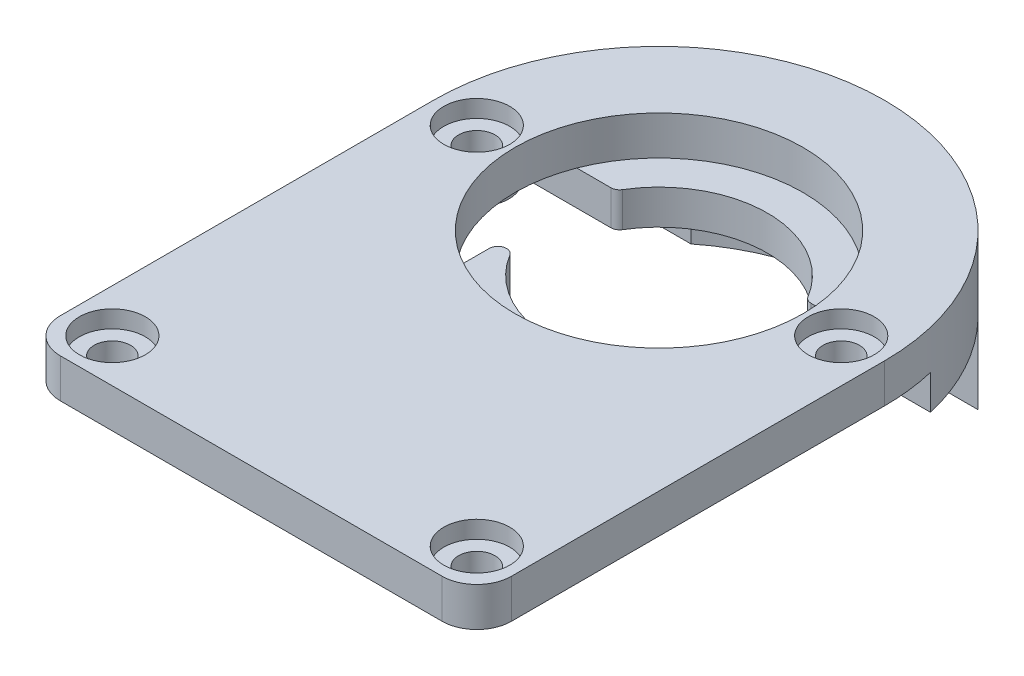
SolidWorks part; units mm, degrees
material "ABS"
ref_plane "正面" through (0, 0, 0) normal (0, 0, 1) x (1, 0, 0)
ref_plane "平面" through (0, 0, 0) normal (0, 1, 0) x (1, 0, 0)
ref_plane "右側面" through (0, 0, 0) normal (1, 0, 0) x (0, 0, -1)
sketch "ｽｹｯﾁ1" plane through (0, 0, 0) normal (0, 1, 0) x (1, 0, 0)
  line L1 (-13, 10.5) -> (13, 10.5)
  line L2 (-13, 10.5) -> (-13, -13)
  line L3 (-13, -13) -> (13, -13)
  line L4 (13, 10.5) -> (13, -13)
  line L5 (-13, 10.5) -> (13, -13) construction
  line L6 (-13, -13) -> (13, 10.5) construction
  circle A0 centre (0, 10.5) radius 13
  circle A1 centre (0, 10.5) radius 8.3
  point P0 (0, -1.25)
  dimension "D1" = 26
  dimension "D3" = 16.6
  dimension "D2" = 23.5
  dimension "D4" = 0
  dimension "D5" = 13
extrude "ﾎﾞｽ - 押し出し1" add sketch "ｽｹｯﾁ1" along normal blind 2.25 contours L1 A0 | L1 A0 | A0 L2 L3 L4 region at (0, 0, -19.0907) region at (10.65, 0, -10.2093) region at (0, 0, 6.0383)
sketch "ｽｹｯﾁ2" plane through (0, 0, 0) normal (0, -1, 0) x (1, 0, 0)
  line L0 (-12.6491, -13.5) -> (-5.4829, -13.5)
  line L1 (-13, 13) -> (13, 13) construction
  line L2 (5.4829, -13.5) -> (12.6491, -13.5)
  arc A0 (-12.6491, -13.5) -> (12.6491, -13.5) centre (0, -10.5) ccw
  arc A1 (-5.4829, -13.5) -> (5.4829, -13.5) centre (0, -10.5) ccw
  circle A2 centre (0, -10.5) radius 8.3 construction
  dimension "D1" = 26
  dimension "D3" = 12.5
  dimension "D2" = 26.5
extrude "ﾎﾞｽ - 押し出し2" add sketch "ｽｹｯﾁ2" along normal blind 2
sketch "ｽｹｯﾁ3" plane through (0, -2, 0) normal (0, -1, 0) x (1, 0, 0)
  line L0 (-9.3808, -19.5) -> (-7.1589, -19.5)
  line L1 (7.1589, -19.5) -> (9.3808, -19.5)
  arc A0 (-9.3808, -19.5) -> (9.3808, -19.5) centre (0, -10.5) ccw
  arc A1 (-7.1589, -19.5) -> (7.1589, -19.5) centre (0, -10.5) ccw
  dimension "D1" = 26
  dimension "D2" = 23
  dimension "D3" = 9
extrude "ﾎﾞｽ - 押し出し3" add sketch "ｽｹｯﾁ3" along normal blind 4.5
sketch "ｽｹｯﾁ4" plane through (0, 0, 0) normal (0, -1, 0) x (1, 0, 0)
  line L1 (-6.25, 6.25) -> (6.25, 6.25)
  line L5 (-6.25, 6.25) -> (6.25, -6.25) construction
  line L6 (-6.25, -6.25) -> (6.25, 6.25) construction
  line L8 (-6.25, -10.5) -> (-6.25, 6.25)
  line L9 (6.25, 6.25) -> (6.25, -10.5)
  arc A0 (6.25, -10.5) -> (-6.25, -10.5) centre (0, -10.5) ccw
  point P0 (0, 0)
  dimension "D2" = 12.5
  dimension "D1" = 12.5
  dimension "D3" = 6.25
extrude "ﾎﾞｽ - 押し出し4" add sketch "ｽｹｯﾁ4" along normal up to surface (2 mm away) up to face at (0, -2, -17.2734)
fillet "ﾌｨﾚｯﾄ1" radius 0.5 4 edges at (-6.25, -1, -10.5) (6.25, -1, -10.5) (-5.4829, -1, -13.5) (5.4829, -1, -13.5)
sketch "ｽｹｯﾁ5" plane through (0, 0, 0) normal (0, -1, 0) x (1, 0, 0)
  line L1 (-10.5, 10.5) -> (10.5, 10.5) construction
  line L2 (-10.5, 10.5) -> (-10.5, -10.5) construction
  line L3 (-10.5, -10.5) -> (10.5, -10.5) construction
  line L4 (10.5, 10.5) -> (10.5, -10.5) construction
  line L5 (-10.5, 10.5) -> (10.5, -10.5) construction
  line L6 (-10.5, -10.5) -> (10.5, 10.5) construction
  circle A0 centre (-10.5, 10.5) radius 1.85
  circle A1 centre (10.5, 10.5) radius 1.85
  circle A2 centre (-10.5, -10.5) radius 1.85
  circle A3 centre (10.5, -10.5) radius 1.85
  point P0 (0, 0)
  dimension "D2" = 3.7
  dimension "D3" = 3.7
  dimension "D4" = 3.7
  dimension "D5" = 3.7
  dimension "D1" = 21
extrude "ﾎﾞｽ - 押し出し5" add sketch "ｽｹｯﾁ5" along normal blind 0.5
hole_wizard "M2 丸平ねじ用座ぐり穴1" positions "ｽｹｯﾁ6" profile "ｽｹｯﾁ7" counterbore size "M2" standard "JIS" end condition up to next
sketch "ｽｹｯﾁ6" plane through (0, 2.25, 0) normal (0, 1, 0) x (1, 0, 0)
  point P0 (10.5, 10.5)
  point P3 (-10.5, 10.5)
  point P6 (-10.5, -10.5)
  point P9 (10.5, -10.5)
sketch "ｽｹｯﾁ7" plane through (10.5, 2.25, -10.5) normal (1, 0, 0) x (0, 0, 1)
  line L0 (0, 0) -> (0, 2.75)
  line L1 (0, 2.75) -> (1.05, 2.75)
  line L3 (1.05, 2.75) -> (1.05, 1)
  line L4 (1.05, 1) -> (1.9, 1)
  line L5 (1.9, 1) -> (1.9, 0)
  line L7 (1.9, 0) -> (0, 0)
  line L11 (0, -6.35) -> (0, 107.95) construction
  dimension "通し穴の直径" = 2.1
  dimension "通し穴の深さ" = 2.75
  dimension "座ぐり穴の直径" = 3.8
  dimension "座ぐり穴の深さ" = 1
fillet "ﾌｨﾚｯﾄ2" radius 2 2 edges at (13, 1.125, 13) (-13, 1.125, 13)
